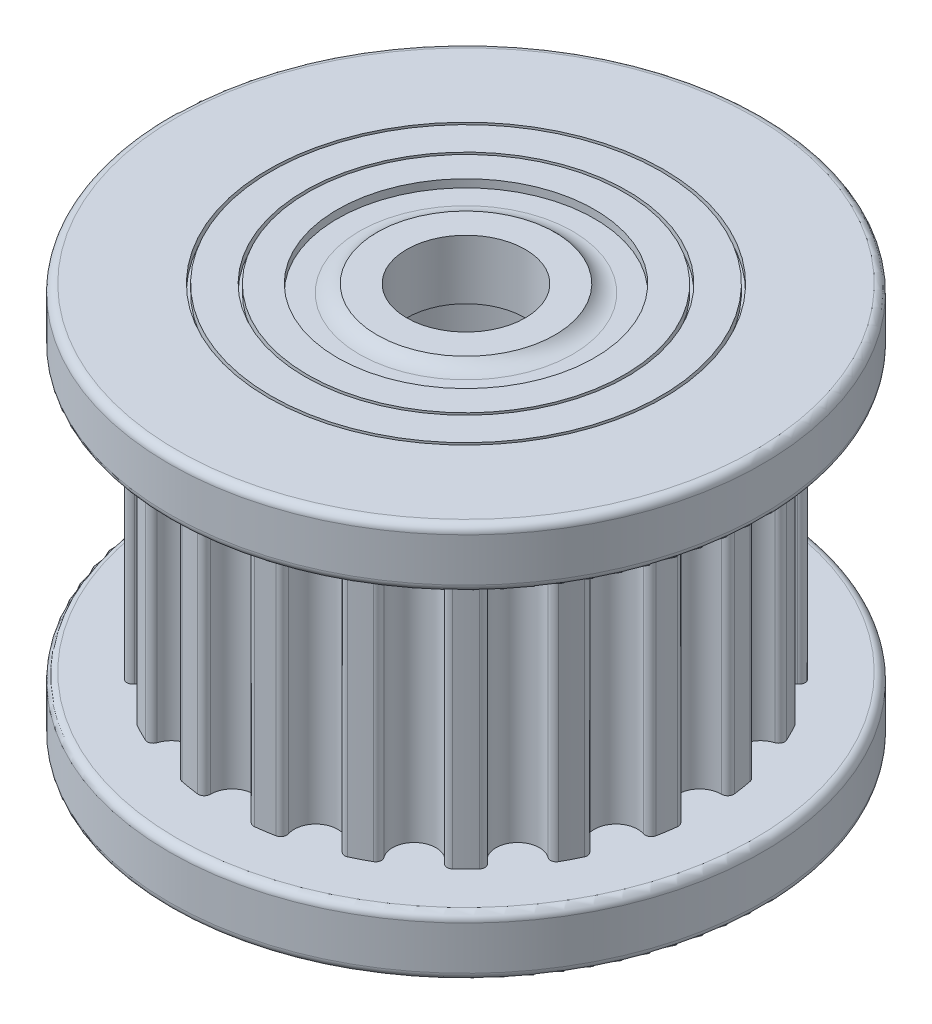
SolidWorks part; units mm, degrees
note: '?' marks a value the reader was unsure of.
material "1060 Alloy"
ref_plane "Спереди" through (0, 0, 0) normal (0, 0, 1) x (1, 0, 0)
ref_plane "Сверху" through (0, 0, 0) normal (0, 1, 0) x (1, 0, 0)
ref_plane "Справа" through (0, 0, 0) normal (1, 0, 0) x (0, 0, -1)
other "Configuration Table"
sketch "Эскиз1" plane through (0, 0, 0) normal (0, 1, 0) x (1, 0, 0)
  circle A0 centre (0, 0) radius 8
  circle A1 centre (0, 0) radius 2.5
  dimension "D1" = 16
  dimension "D2" = 5
extrude "Бобышка-Вытянуть1" add sketch "Эскиз1" along normal blind 7.45
sketch "Эскиз2" plane through (0, 7.45, 0) normal (0, 1, 0) x (1, 0, 0)
  arc A0 (-2.5575, 5.549) -> (-2.986, 5.3307) centre (0, 0) ccw
  circle A1 centre (0, 0) radius 2.5 construction
  circle A2 centre (0, 0) radius 2.5
  arc A3 (-0.55, 5.9169) -> (0.55, 5.9169) centre (0, 5.91) ccw
  arc A4 (1.3054, 5.7972) -> (2.3515, 5.4573) centre (1.8263, 5.6207) ccw
  arc A5 (3.0329, 5.1101) -> (3.9228, 4.4636) centre (3.4738, 4.7813) ccw
  arc A6 (4.4636, 3.9228) -> (5.1101, 3.0329) centre (4.7813, 3.4738) ccw
  arc A7 (5.4573, 2.3515) -> (5.7972, 1.3054) centre (5.6207, 1.8263) ccw
  arc A8 (5.9169, 0.55) -> (5.9169, -0.55) centre (5.91, 0) ccw
  arc A9 (5.7972, -1.3054) -> (5.4573, -2.3515) centre (5.6207, -1.8263) ccw
  arc A10 (5.1101, -3.0329) -> (4.4636, -3.9228) centre (4.7813, -3.4738) ccw
  arc A11 (3.9228, -4.4636) -> (3.0329, -5.1101) centre (3.4738, -4.7813) ccw
  arc A12 (2.3515, -5.4573) -> (1.3054, -5.7972) centre (1.8263, -5.6207) ccw
  arc A13 (0.55, -5.9169) -> (-0.55, -5.9169) centre (0, -5.91) ccw
  arc A14 (-1.3054, -5.7972) -> (-2.3515, -5.4573) centre (-1.8263, -5.6207) ccw
  arc A15 (-3.0329, -5.1101) -> (-3.9228, -4.4636) centre (-3.4738, -4.7813) ccw
  arc A16 (-4.4636, -3.9228) -> (-5.1101, -3.0329) centre (-4.7813, -3.4738) ccw
  arc A17 (-5.4573, -2.3515) -> (-5.7972, -1.3054) centre (-5.6207, -1.8263) ccw
  arc A18 (-5.9169, -0.55) -> (-5.9169, 0.55) centre (-5.91, 0) ccw
  arc A19 (-5.7972, 1.3054) -> (-5.4573, 2.3515) centre (-5.6207, 1.8263) ccw
  arc A20 (-5.1101, 3.0329) -> (-4.4636, 3.9228) centre (-4.7813, 3.4738) ccw
  arc A21 (-3.9228, 4.4636) -> (-3.0329, 5.1101) centre (-3.4738, 4.7813) ccw
  arc A22 (-2.3515, 5.4573) -> (-1.3054, 5.7972) centre (-1.8263, 5.6207) ccw
  arc A23 (-4.147, 4.4871) -> (-4.4871, 4.147) centre (0, 0) ccw
  arc A24 (-0.7176, 6.0677) -> (-1.1926, 5.9925) centre (0, 0) ccw
  arc A25 (1.1926, 5.9925) -> (0.7176, 6.0677) centre (0, 0) ccw
  arc A26 (2.986, 5.3307) -> (2.5575, 5.549) centre (0, 0) ccw
  arc A27 (4.4871, 4.147) -> (4.147, 4.4871) centre (0, 0) ccw
  arc A28 (5.549, 2.5575) -> (5.3307, 2.986) centre (0, 0) ccw
  arc A29 (6.0677, 0.7176) -> (5.9925, 1.1926) centre (0, 0) ccw
  arc A30 (-5.3307, 2.986) -> (-5.549, 2.5575) centre (0, 0) ccw
  arc A31 (-5.9925, 1.1926) -> (-6.0677, 0.7176) centre (0, 0) ccw
  arc A32 (-6.0677, -0.7176) -> (-5.9925, -1.1926) centre (0, 0) ccw
  arc A33 (-5.549, -2.5575) -> (-5.3307, -2.986) centre (0, 0) ccw
  arc A34 (-4.4871, -4.147) -> (-4.147, -4.4871) centre (0, 0) ccw
  arc A35 (-2.986, -5.3307) -> (-2.5575, -5.549) centre (0, 0) ccw
  arc A36 (5.9925, -1.1926) -> (6.0677, -0.7176) centre (0, 0) ccw
  arc A37 (5.3307, -2.986) -> (5.549, -2.5575) centre (0, 0) ccw
  arc A38 (4.147, -4.4871) -> (4.4871, -4.147) centre (0, 0) ccw
  arc A39 (2.5575, -5.549) -> (2.986, -5.3307) centre (0, 0) ccw
  arc A40 (0.7176, -6.0677) -> (1.1926, -5.9925) centre (0, 0) ccw
  arc A41 (-1.1926, -5.9925) -> (-0.7176, -6.0677) centre (0, 0) ccw
  arc A42 (5.9169, 0.55) -> (6.0677, 0.7176) centre (5.9188, 0.6999) ccw
  arc A43 (5.7972, 1.3054) -> (5.9925, 1.1926) centre (5.8454, 1.1633) cw
  arc A44 (5.4573, 2.3515) -> (5.549, 2.5575) centre (5.4128, 2.4947) ccw
  arc A45 (5.1101, 3.0329) -> (5.3307, 2.986) centre (5.1998, 2.9127) cw
  arc A46 (5.1101, -3.0329) -> (5.3307, -2.986) centre (5.1998, -2.9127) ccw
  arc A47 (5.4573, -2.3515) -> (5.549, -2.5575) centre (5.4128, -2.4947) cw
  arc A48 (5.7972, -1.3054) -> (5.9925, -1.1926) centre (5.8454, -1.1633) ccw
  arc A49 (5.9169, -0.55) -> (6.0677, -0.7176) centre (5.9188, -0.6999) cw
  arc A50 (3.9228, -4.4636) -> (4.147, -4.4871) centre (4.0452, -4.377) ccw
  arc A51 (4.4636, -3.9228) -> (4.4871, -4.147) centre (4.377, -4.0452) cw
  arc A52 (3.0329, -5.1101) -> (2.986, -5.3307) centre (2.9127, -5.1998) cw
  arc A53 (1.3054, -5.7972) -> (1.1926, -5.9925) centre (1.1633, -5.8454) cw
  arc A54 (0.55, -5.9169) -> (0.7176, -6.0677) centre (0.6999, -5.9188) ccw
  arc A55 (-0.55, -5.9169) -> (-0.7176, -6.0677) centre (-0.6999, -5.9188) cw
  arc A56 (-1.3054, -5.7972) -> (-1.1926, -5.9925) centre (-1.1633, -5.8454) ccw
  arc A57 (-2.3515, -5.4573) -> (-2.5575, -5.549) centre (-2.4947, -5.4128) cw
  arc A58 (-3.0329, -5.1101) -> (-2.986, -5.3307) centre (-2.9127, -5.1998) ccw
  arc A59 (-3.9228, -4.4636) -> (-4.147, -4.4871) centre (-4.0452, -4.377) cw
  arc A60 (-4.4636, -3.9228) -> (-4.4871, -4.147) centre (-4.377, -4.0452) ccw
  arc A61 (-5.9169, -0.55) -> (-6.0677, -0.7176) centre (-5.9188, -0.6999) ccw
  arc A62 (-5.7972, -1.3054) -> (-5.9925, -1.1926) centre (-5.8454, -1.1633) cw
  arc A63 (-5.4573, -2.3515) -> (-5.549, -2.5575) centre (-5.4128, -2.4947) ccw
  arc A64 (-5.1101, -3.0329) -> (-5.3307, -2.986) centre (-5.1998, -2.9127) cw
  arc A65 (-5.1101, 3.0329) -> (-5.3307, 2.986) centre (-5.1998, 2.9127) ccw
  arc A66 (-5.4573, 2.3515) -> (-5.549, 2.5575) centre (-5.4128, 2.4947) cw
  arc A67 (-5.7972, 1.3054) -> (-5.9925, 1.1926) centre (-5.8454, 1.1633) ccw
  arc A68 (-5.9169, 0.55) -> (-6.0677, 0.7176) centre (-5.9188, 0.6999) cw
  arc A69 (-4.4636, 3.9228) -> (-4.4871, 4.147) centre (-4.377, 4.0452) cw
  arc A70 (-3.9228, 4.4636) -> (-4.147, 4.4871) centre (-4.0452, 4.377) ccw
  arc A71 (-3.0329, 5.1101) -> (-2.986, 5.3307) centre (-2.9127, 5.1998) cw
  arc A72 (-2.3515, 5.4573) -> (-2.5575, 5.549) centre (-2.4947, 5.4128) ccw
  arc A73 (-1.3054, 5.7972) -> (-1.1926, 5.9925) centre (-1.1633, 5.8454) cw
  arc A74 (-0.55, 5.9169) -> (-0.7176, 6.0677) centre (-0.6999, 5.9188) ccw
  arc A75 (4.4636, 3.9228) -> (4.4871, 4.147) centre (4.377, 4.0452) ccw
  arc A76 (3.9228, 4.4636) -> (4.147, 4.4871) centre (4.0452, 4.377) cw
  arc A77 (0.55, 5.9169) -> (0.7176, 6.0677) centre (0.6999, 5.9188) cw
  arc A78 (1.3054, 5.7972) -> (1.1926, 5.9925) centre (1.1633, 5.8454) ccw
  arc A79 (3.0329, 5.1101) -> (2.986, 5.3307) centre (2.9127, 5.1998) ccw
  arc A80 (2.3515, 5.4573) -> (2.5575, 5.549) centre (2.4947, 5.4128) cw
  arc A81 (2.3515, -5.4573) -> (2.5575, -5.549) centre (2.4947, -5.4128) ccw
  point P69 (0, 0)
  point P135 (-0.5205, 6.0878)
  point P142 (0.5205, 6.0878)
  dimension "D1" = 12.22
  dimension "D2" = 1.1
  dimension "D3" = 0.75
  dimension "D5" = 0.15
  dimension "D6" = 0.15
  dimension "D4" = 20
extrude "Бобышка-Вытянуть2" add sketch "Эскиз2" along normal blind 7
sketch "Эскиз3" plane through (0, 14.45, 0) normal (0, 1, 0) x (1, 0, 0)
  circle A0 centre (0, 0) radius 2.5 construction
  circle A1 centre (0, 0) radius 2.5
  circle A2 centre (0, 0) radius 8 construction
  circle A3 centre (0, 0) radius 8
extrude "Бобышка-Вытянуть3" add sketch "Эскиз3" along normal blind 1.55
sketch "Эскиз4" plane through (0, 0, 0) normal (0, 0, 1) x (1, 0, 0)
  line L0 (-8, 3.725) -> (8, 3.725) construction
  line L1 (-8, 7.45) -> (-8, 0) construction
  line L2 (8, 0) -> (8, 7.45) construction
  circle A0 centre (0, 3.725) radius 1.25
  dimension "D1" = 2.5
extrude "Вырез-Вытянуть1" cut sketch "Эскиз4" along normal up to surface (7.9017 mm away)
sketch "Эскиз5" plane through (0, 0, 0) normal (1, 0, 0) x (0, 0, -1)
  line L0 (8, 3.725) -> (-7.9017, 3.725) construction
  line L1 (8, 0) -> (8, 7.45) construction
  circle A0 centre (0, 3.725) radius 1.25
  spline S1 degree 2 poles (-8, 4.975) (-7.8047, 3.725) (-8, 2.475) knots 0 0 0 1 1 1 weights 0.00675 0.008 0.00925 construction
  dimension "D1" = 2.5
extrude "Вырез-Вытянуть2" cut sketch "Эскиз5" along normal up to surface (7.9017 mm away)
sketch "Минимальный радиус ремня" plane through (0, 7.45, 0) normal (0, 1, 0) x (1, 0, 0)
  circle A0 centre (0, 0) radius 5.36
  arc A2 (-2.986, -5.3307) -> (-2.5575, -5.549) centre (0, 0) ccw construction
  dimension "D1" = 0.75
  dimension "D2" = 10.72
chamfer "Фаска1" distance 1 angle 30 2 edges at (0, 14.45, 8) (0, 7.45, 8)
ref_axis "Ось1" through (0, 16, 0) along (0, -1, 0)?
sketch "Sketch1" plane through (0, 16, 0) normal (0, 1, 0) x (1, 0, 0)
  circle A0 centre (0, 0) radius 8
  circle A1 centre (0, 0) radius 8 construction
extrude "Cut-Extrude1" cut sketch "Sketch1" against normal blind 0.75 and the other way through all
sketch "Sketch2" plane through (0, 14.45, 0) normal (0, -1, 0) x (1, 0, 0)
  circle A0 centre (0, 0) radius 7.5
  dimension "D1" = 15
extrude "Boss-Extrude1" add sketch "Sketch2" against normal blind 1.5
sketch "Sketch3" plane through (0, 0, 0) normal (0, -1, 0) x (1, 0, 0)
  circle A0 centre (0, 0) radius 8
  circle A1 centre (0, 0) radius 8 construction
extrude "Cut-Extrude2" cut sketch "Sketch3" against normal blind 7
sketch "Sketch4" plane through (0, 7.45, 0) normal (0, 1, 0) x (1, 0, 0)
  circle A0 centre (0, 0) radius 7.5
  circle A1 centre (0, 0) radius 7.5 construction
extrude "Boss-Extrude2" add sketch "Sketch4" against normal blind 1.5
sketch "Sketch5" plane through (0, 15.95, 0) normal (0, 1, 0) x (1, 0, 0)
  circle A0 centre (0, 0) radius 5
  dimension "D1" = 10
extrude "Cut-Extrude4" cut sketch "Sketch5" against normal blind 0.2
sketch "Sketch7" plane through (0, 5.95, 0) normal (0, -1, 0) x (1, 0, 0)
  circle A0 centre (0, 0) radius 5
  dimension "D1" = 10
extrude "Cut-Extrude5" cut sketch "Sketch7" against normal blind 0.2
sketch "Sketch8" plane through (0, 6.15, 0) normal (0, -1, 0) x (1, 0, 0)
  circle A0 centre (0, 0) radius 4.075
  circle A1 centre (0, 0) radius 4.925
  dimension "D1" = 8.15
  dimension "D2" = 9.85
extrude "Boss-Extrude3" add sketch "Sketch8" along normal blind 0.2
sketch "Sketch9" plane through (0, 15.75, 0) normal (0, 1, 0) x (1, 0, 0)
  circle A0 centre (0, 0) radius 4.075
  circle A1 centre (0, 0) radius 4.925
  dimension "D1" = 8.15
  dimension "D2" = 9.85
extrude "Boss-Extrude4" add sketch "Sketch9" along normal blind 0.2
sketch "Sketch12" plane through (0, 15.75, 0) normal (0, 1, 0) x (1, 0, 0)
  circle A0 centre (0, 0) radius 4
  circle A1 centre (0, 0) radius 3.25
  dimension "D1" = 8
  dimension "D2" = 6.5
extrude "Boss-Extrude5" add sketch "Sketch12" along normal blind 0.2
sketch "Sketch13" plane through (0, 6.15, 0) normal (0, -1, 0) x (1, 0, 0)
  circle A0 centre (0, 0) radius 4
  circle A1 centre (0, 0) radius 3.25
  dimension "D1" = 8
  dimension "D2" = 6.5
extrude "Boss-Extrude6" add sketch "Sketch13" along normal blind 0.2
sketch "Sketch14" plane through (0, 15.75, 0) normal (0, 1, 0) x (1, 0, 0)
  circle A0 centre (0, 0) radius 2.25
  circle A1 centre (0, 0) radius 1.5
  dimension "D1" = 4.5
  dimension "D2" = 3
extrude "Boss-Extrude7" add sketch "Sketch14" along normal blind 0.2
sketch "Sketch15" plane through (0, 6.15, 0) normal (0, -1, 0) x (1, 0, 0)
  circle A0 centre (0, 0) radius 2.25
  circle A1 centre (0, 0) radius 1.5
  dimension "D1" = 4.5
  dimension "D2" = 3
extrude "Boss-Extrude8" add sketch "Sketch15" along normal blind 0.2
sketch "Sketch16" plane through (0, 15.75, 0) normal (0, 1, 0) x (1, 0, 0)
  circle A0 centre (0, 0) radius 1.5
  circle A1 centre (0, 0) radius 1.5 construction
extrude "Cut-Extrude6" cut sketch "Sketch16" against normal blind 10.2
fillet "Fillet1" radius 0.6 2 edges at (0, 6.15, -2.25) (0, 15.75, 2.25)
fillet "Fillet2" radius 0.2 4 edges at (0, 15.95, -7.5) (0, 14.45, -7.5) (0, 7.45, 7.5) (0, 5.95, 7.5)
sketch "Sketch18" plane through (0, 7, 0) normal (0, -1, 0) x (1, 0, 0)
  circle A0 centre (0, 0) radius 7.7794
  circle A1 centre (0, 0) radius 7.7794 construction
  circle A2 centre (0, 0) radius 7.5
  circle A3 centre (0, 0) radius 7.5 construction
extrude "Cut-Extrude7" cut sketch "Sketch18" against normal blind 1
sketch "Sketch19" plane through (0, 15.25, 0) normal (0, 1, 0) x (1, 0, 0)
  circle A0 centre (0, 0) radius 8
  circle A1 centre (0, 0) radius 7.5
  circle A2 centre (0, 0) radius 7.5 construction
  circle A3 centre (0, 0) radius 8 construction
extrude "Cut-Extrude8" cut sketch "Sketch19" against normal blind 1
